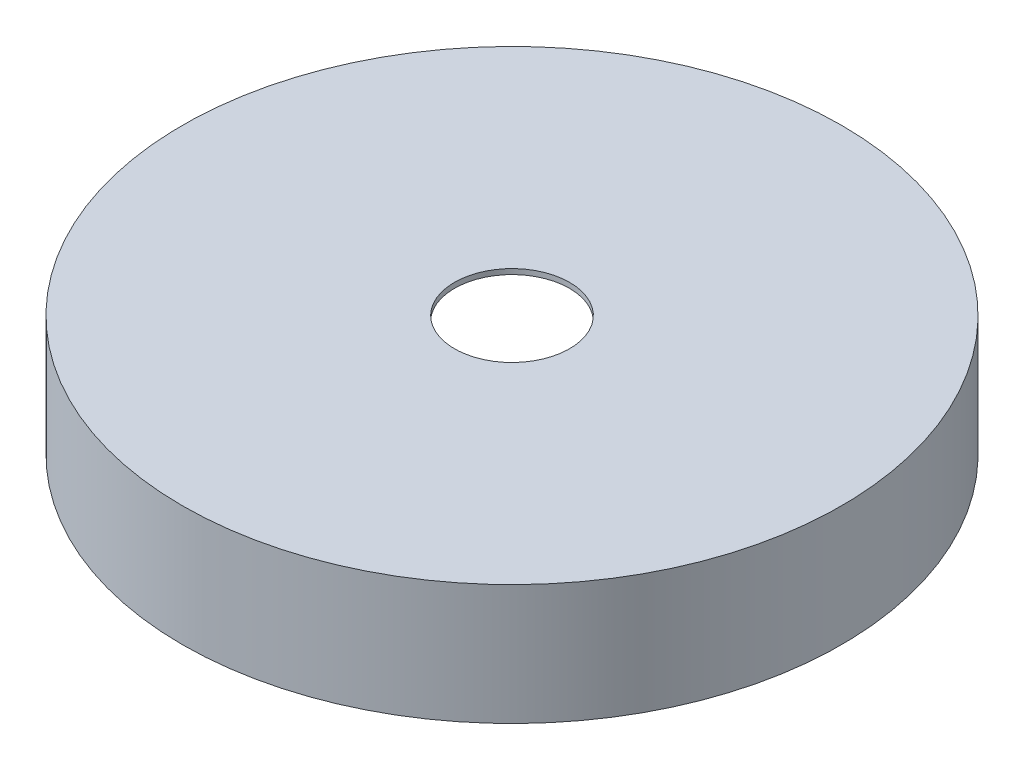
SolidWorks part; units mm, degrees
ref_plane "Front Plane" through (0, 0, 0) normal (0, 0, 1) x (1, 0, 0)
ref_plane "Top Plane" through (0, 0, 0) normal (0, 1, 0) x (1, 0, 0)
ref_plane "Right Plane" through (0, 0, 0) normal (1, 0, 0) x (0, 0, -1)
sketch "Sketch1" plane through (0, 0, 0) normal (0, 0, 1) x (1, 0, 0)
  line L0 (-160.02, 0) -> (-160.02, 58.42)
  line L2 (55, 0) -> (-55, 0) construction
  line L3 (-27.94, 55.88) -> (-157.48, 55.88)
  line L4 (-157.48, 0) -> (-157.48, 55.88)
  line L5 (0, -55) -> (0, 55) construction
  line L7 (-160.02, 58.42) -> (-27.94, 58.42)
  line L8 (-27.94, 58.42) -> (-27.94, 55.88)
  line L9 (-157.48, 0) -> (-160.02, 0)
  point P0 (0, 0)
  dimension "D1" = 160.02
  dimension "D2" = 58.42
  dimension "D3" = 2.54
  dimension "D4" = 2.54
  dimension "D5" = 27.94
ref_axis "Axis1" through (0, -2.54, 0) along (0, 1, 0)
revolve "Revolve1" add sketch "Sketch1" angle 360 about axis through (0, -2.54, 0) along (0, 1, 0)
